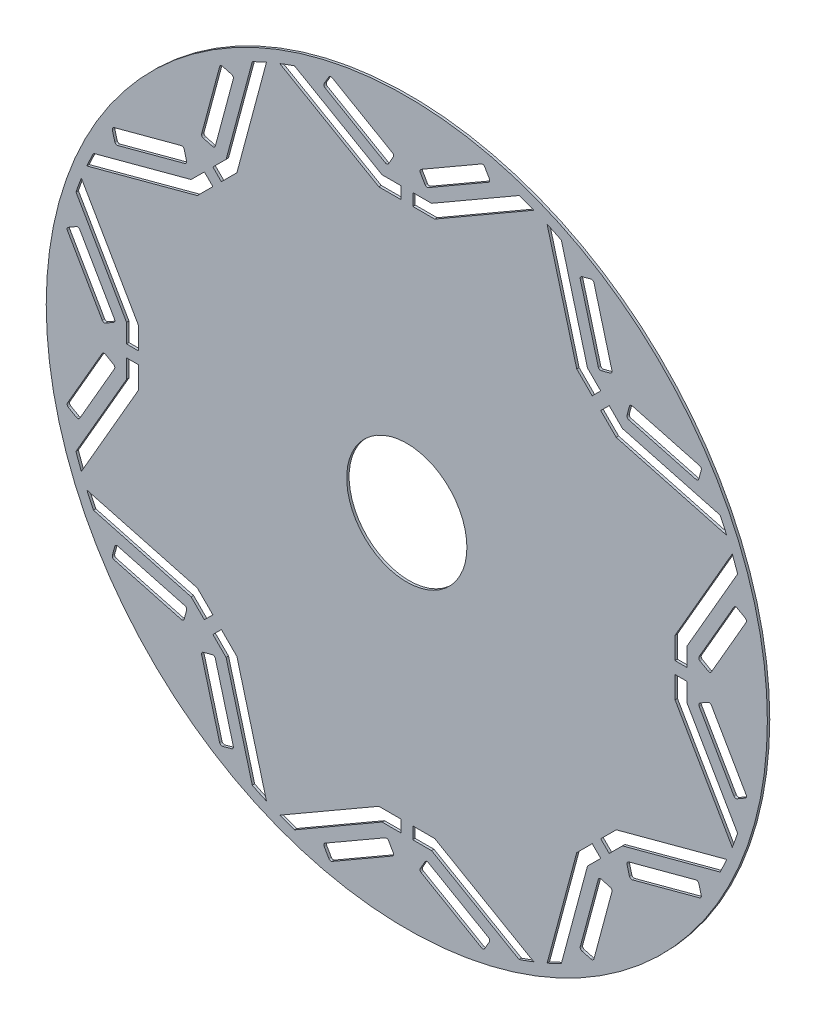
SolidWorks part; units mm, degrees
ref_plane "Front Plane" through (0, 0, 0) normal (0, 0, 1) x (1, 0, 0)
ref_plane "Top Plane" through (0, 0, 0) normal (0, 1, 0) x (1, 0, 0)
ref_plane "Right Plane" through (0, 0, 0) normal (1, 0, 0) x (0, 0, -1)
sketch "Rotor sketch" plane through (0, 0, 0) normal (0, 0, 1) x (1, 0, 0)
  line L0 (0, 0) -> (0, 45) construction
  line L1 (2.6839, 36.4771) -> (10.2011, 40.8171)
  line L2 (2.2741, 36.5869) -> (1.6891, 37.6002)
  line L3 (10.3109, 41.2269) -> (9.7259, 42.2402)
  line L4 (1.7989, 38.01) -> (9.3161, 42.35)
  line L5 (2.4241, 36.3271) -> (9.5759, 42.5) construction
  line L6 (10.4609, 40.9671) -> (1.5391, 37.86) construction
  line L7 (-10.4609, 40.9671) -> (-1.5391, 37.86) construction
  line L8 (-2.4241, 36.3271) -> (-9.5759, 42.5) construction
  line L9 (-1.7989, 38.01) -> (-9.3161, 42.35)
  line L10 (-10.3109, 41.2269) -> (-9.7259, 42.2402)
  line L11 (-2.2741, 36.5869) -> (-1.6891, 37.6002)
  line L12 (-2.6839, 36.4771) -> (-10.2011, 40.8171)
  line L13 (25.6051, 28.1492) -> (23.3585, 36.5334)
  line L14 (24.2628, 27.4789) -> (25.3929, 27.7818)
  line L15 (23.8954, 27.6911) -> (21.6488, 36.0753)
  line L16 (21.861, 36.4427) -> (22.9911, 36.7455)
  line L17 (27.4789, 24.2628) -> (27.7818, 25.3929)
  line L18 (28.1492, 25.6051) -> (36.5334, 23.3585)
  line L19 (36.4427, 21.861) -> (36.7455, 22.9911)
  line L20 (27.6911, 23.8954) -> (36.0753, 21.6488)
  line L21 (38.01, 1.7989) -> (42.35, 9.3161)
  line L22 (36.5869, 2.2741) -> (37.6002, 1.6891)
  line L23 (36.4771, 2.6839) -> (40.8171, 10.2011)
  line L24 (41.2269, 10.3109) -> (42.2402, 9.7259)
  line L25 (36.5869, -2.2741) -> (37.6002, -1.6891)
  line L26 (38.01, -1.7989) -> (42.35, -9.3161)
  line L27 (41.2269, -10.3109) -> (42.2402, -9.7259)
  line L28 (36.4771, -2.6839) -> (40.8171, -10.2011)
  line L29 (28.1492, -25.6051) -> (36.5334, -23.3585)
  line L30 (27.4789, -24.2628) -> (27.7818, -25.3929)
  line L31 (27.6911, -23.8954) -> (36.0753, -21.6488)
  line L32 (36.4427, -21.861) -> (36.7455, -22.9911)
  line L33 (24.2628, -27.4789) -> (25.3929, -27.7818)
  line L34 (25.6051, -28.1492) -> (23.3585, -36.5334)
  line L35 (21.861, -36.4427) -> (22.9911, -36.7455)
  line L36 (23.8954, -27.6911) -> (21.6488, -36.0753)
  line L37 (1.7989, -38.01) -> (9.3161, -42.35)
  line L38 (2.2741, -36.5869) -> (1.6891, -37.6002)
  line L39 (2.6839, -36.4771) -> (10.2011, -40.8171)
  line L40 (10.3109, -41.2269) -> (9.7259, -42.2402)
  line L41 (-2.2741, -36.5869) -> (-1.6891, -37.6002)
  line L42 (-1.7989, -38.01) -> (-9.3161, -42.35)
  line L43 (-10.3109, -41.2269) -> (-9.7259, -42.2402)
  line L44 (-2.6839, -36.4771) -> (-10.2011, -40.8171)
  line L45 (-25.6051, -28.1492) -> (-23.3585, -36.5334)
  line L46 (-24.2628, -27.4789) -> (-25.3929, -27.7818)
  line L47 (-23.8954, -27.6911) -> (-21.6488, -36.0753)
  line L48 (-21.861, -36.4427) -> (-22.9911, -36.7455)
  line L49 (-27.4789, -24.2628) -> (-27.7818, -25.3929)
  line L50 (-28.1492, -25.6051) -> (-36.5334, -23.3585)
  line L51 (-36.4427, -21.861) -> (-36.7455, -22.9911)
  line L52 (-27.6911, -23.8954) -> (-36.0753, -21.6488)
  line L53 (-38.01, -1.7989) -> (-42.35, -9.3161)
  line L54 (-36.5869, -2.2741) -> (-37.6002, -1.6891)
  line L55 (-36.4771, -2.6839) -> (-40.8171, -10.2011)
  line L56 (-41.2269, -10.3109) -> (-42.2402, -9.7259)
  line L57 (-36.5869, 2.2741) -> (-37.6002, 1.6891)
  line L58 (-38.01, 1.7989) -> (-42.35, 9.3161)
  line L59 (-41.2269, 10.3109) -> (-42.2402, 9.7259)
  line L60 (-36.4771, 2.6839) -> (-40.8171, 10.2011)
  line L61 (-28.1492, 25.6051) -> (-36.5334, 23.3585)
  line L62 (-27.4789, 24.2628) -> (-27.7818, 25.3929)
  line L63 (-27.6911, 23.8954) -> (-36.0753, 21.6488)
  line L64 (-36.4427, 21.861) -> (-36.7455, 22.9911)
  line L65 (-24.2628, 27.4789) -> (-25.3929, 27.7818)
  line L66 (-25.6051, 28.1492) -> (-23.3585, 36.5334)
  line L67 (-21.861, 36.4427) -> (-22.9911, 36.7455)
  line L68 (-23.8954, 27.6911) -> (-21.6488, 36.0753)
  line L69 (0, 0) -> (-9.8912, 43.8995) construction
  circle A0 centre (0, 0) radius 45
  circle A1 centre (0, 0) radius 7.5
  arc A2 (-21.861, 36.4427) -> (-21.6488, 36.0753) centre (-21.9386, 36.153) cw
  arc A3 (-23.3585, 36.5334) -> (-22.9911, 36.7455) centre (-23.0688, 36.4558) cw
  arc A4 (-24.2628, 27.4789) -> (-23.8954, 27.6911) centre (-24.1852, 27.7687) ccw
  arc A5 (-25.3929, 27.7818) -> (-25.6051, 28.1492) centre (-25.3153, 28.0715) cw
  arc A6 (-27.4789, 24.2628) -> (-27.6911, 23.8954) centre (-27.7687, 24.1852) cw
  arc A7 (-28.1492, 25.6051) -> (-27.7818, 25.3929) centre (-28.0715, 25.3153) cw
  arc A8 (-36.5334, 23.3585) -> (-36.7455, 22.9911) centre (-36.4558, 23.0688) ccw
  arc A9 (-36.0753, 21.6488) -> (-36.4427, 21.861) centre (-36.153, 21.9386) cw
  arc A10 (-36.5869, 2.2741) -> (-36.4771, 2.6839) centre (-36.7369, 2.5339) ccw
  arc A11 (-37.6002, 1.6891) -> (-38.01, 1.7989) centre (-37.7502, 1.9489) cw
  arc A12 (-41.2269, 10.3109) -> (-40.8171, 10.2011) centre (-41.0769, 10.0511) cw
  arc A13 (-42.35, 9.3161) -> (-42.2402, 9.7259) centre (-42.0902, 9.4661) cw
  arc A14 (-36.5869, -2.2741) -> (-36.4771, -2.6839) centre (-36.7369, -2.5339) cw
  arc A15 (-38.01, -1.7989) -> (-37.6002, -1.6891) centre (-37.7502, -1.9489) cw
  arc A16 (-42.35, -9.3161) -> (-42.2402, -9.7259) centre (-42.0902, -9.4661) ccw
  arc A17 (-40.8171, -10.2011) -> (-41.2269, -10.3109) centre (-41.0769, -10.0511) cw
  arc A18 (-36.5334, -23.3585) -> (-36.7455, -22.9911) centre (-36.4558, -23.0688) cw
  arc A19 (-36.4427, -21.861) -> (-36.0753, -21.6488) centre (-36.153, -21.9386) cw
  arc A20 (-27.4789, -24.2628) -> (-27.6911, -23.8954) centre (-27.7687, -24.1852) ccw
  arc A21 (-27.7818, -25.3929) -> (-28.1492, -25.6051) centre (-28.0715, -25.3153) cw
  arc A22 (-24.2628, -27.4789) -> (-23.8954, -27.6911) centre (-24.1852, -27.7687) cw
  arc A23 (-25.6051, -28.1492) -> (-25.3929, -27.7818) centre (-25.3153, -28.0715) cw
  arc A24 (-23.3585, -36.5334) -> (-22.9911, -36.7455) centre (-23.0688, -36.4558) ccw
  arc A25 (-21.6488, -36.0753) -> (-21.861, -36.4427) centre (-21.9386, -36.153) cw
  arc A26 (-10.3109, -41.2269) -> (-10.2011, -40.8171) centre (-10.0511, -41.0769) cw
  arc A27 (-9.3161, -42.35) -> (-9.7259, -42.2402) centre (-9.4661, -42.0902) cw
  arc A28 (-1.6891, -37.6002) -> (-1.7989, -38.01) centre (-1.9489, -37.7502) cw
  arc A29 (-2.2741, -36.5869) -> (-2.6839, -36.4771) centre (-2.5339, -36.7369) ccw
  arc A30 (10.2011, -40.8171) -> (10.3109, -41.2269) centre (10.0511, -41.0769) cw
  arc A31 (9.3161, -42.35) -> (9.7259, -42.2402) centre (9.4661, -42.0902) ccw
  arc A32 (1.7989, -38.01) -> (1.6891, -37.6002) centre (1.9489, -37.7502) cw
  arc A33 (2.2741, -36.5869) -> (2.6839, -36.4771) centre (2.5339, -36.7369) cw
  arc A34 (23.3585, -36.5334) -> (22.9911, -36.7455) centre (23.0688, -36.4558) cw
  arc A35 (21.861, -36.4427) -> (21.6488, -36.0753) centre (21.9386, -36.153) cw
  arc A36 (24.2628, -27.4789) -> (23.8954, -27.6911) centre (24.1852, -27.7687) ccw
  arc A37 (25.3929, -27.7818) -> (25.6051, -28.1492) centre (25.3153, -28.0715) cw
  arc A38 (28.1492, -25.6051) -> (27.7818, -25.3929) centre (28.0715, -25.3153) cw
  arc A39 (27.4789, -24.2628) -> (27.6911, -23.8954) centre (27.7687, -24.1852) cw
  arc A40 (36.5334, -23.3585) -> (36.7455, -22.9911) centre (36.4558, -23.0688) ccw
  arc A41 (36.0753, -21.6488) -> (36.4427, -21.861) centre (36.153, -21.9386) cw
  arc A42 (41.2269, -10.3109) -> (40.8171, -10.2011) centre (41.0769, -10.0511) cw
  arc A43 (42.35, -9.3161) -> (42.2402, -9.7259) centre (42.0902, -9.4661) cw
  arc A44 (37.6002, -1.6891) -> (38.01, -1.7989) centre (37.7502, -1.9489) cw
  arc A45 (36.5869, -2.2741) -> (36.4771, -2.6839) centre (36.7369, -2.5339) ccw
  arc A46 (38.01, 1.7989) -> (37.6002, 1.6891) centre (37.7502, 1.9489) cw
  arc A47 (36.5869, 2.2741) -> (36.4771, 2.6839) centre (36.7369, 2.5339) cw
  arc A48 (40.8171, 10.2011) -> (41.2269, 10.3109) centre (41.0769, 10.0511) cw
  arc A49 (42.35, 9.3161) -> (42.2402, 9.7259) centre (42.0902, 9.4661) ccw
  arc A50 (36.4427, 21.861) -> (36.0753, 21.6488) centre (36.153, 21.9386) cw
  arc A51 (36.5334, 23.3585) -> (36.7455, 22.9911) centre (36.4558, 23.0688) cw
  arc A52 (27.4789, 24.2628) -> (27.6911, 23.8954) centre (27.7687, 24.1852) ccw
  arc A53 (27.7818, 25.3929) -> (28.1492, 25.6051) centre (28.0715, 25.3153) cw
  arc A54 (24.2628, 27.4789) -> (23.8954, 27.6911) centre (24.1852, 27.7687) cw
  arc A55 (25.6051, 28.1492) -> (25.3929, 27.7818) centre (25.3153, 28.0715) cw
  arc A56 (23.3585, 36.5334) -> (22.9911, 36.7455) centre (23.0688, 36.4558) ccw
  arc A57 (21.6488, 36.0753) -> (21.861, 36.4427) centre (21.9386, 36.153) cw
  arc A58 (10.2011, 40.8171) -> (10.3109, 41.2269) centre (10.0511, 41.0769) ccw
  arc A59 (9.7259, 42.2402) -> (9.3161, 42.35) centre (9.4661, 42.0902) ccw
  arc A60 (1.6891, 37.6002) -> (1.7989, 38.01) centre (1.9489, 37.7502) cw
  arc A61 (2.2741, 36.5869) -> (2.6839, 36.4771) centre (2.5339, 36.7369) ccw
  arc A62 (-10.2011, 40.8171) -> (-10.3109, 41.2269) centre (-10.0511, 41.0769) cw
  arc A63 (-2.6839, 36.4771) -> (-2.2741, 36.5869) centre (-2.5339, 36.7369) ccw
  arc A64 (-1.6891, 37.6002) -> (-1.7989, 38.01) centre (-1.9489, 37.7502) ccw
  arc A65 (-9.7259, 42.2402) -> (-9.3161, 42.35) centre (-9.4661, 42.0902) cw
  point P6 (6, 39.4136)
  point P16 (-6, 39.4136)
  point P74 (0, 0)
  dimension "D6" = 90
  dimension "D7" = 15
  dimension "D10" = 0.3
  dimension "D1" = 9.28
  dimension "D2" = 1.77
  dimension "D3" = 60
  dimension "D4" = 6
  dimension "D5" = 2.5
  dimension "D9" = 1.4346
  dimension "D8" = 8
extrude "Boss-Extrude1" add sketch "Rotor sketch" along normal mid plane 0.3
sketch "Saliency grooves" plane through (0, 0, 0.15) normal (0, 0, 1) x (1, 0, 0)
  line L0 (-12.8371, 38.875) -> (-3.4878, 33.4771)
  line L3 (-14.0139, 41.2864) -> (-3.0859, 34.9771)
  line L4 (0.75, 34.9771) -> (3.0859, 34.9771)
  line L5 (-3.4878, 33.4771) -> (-14.0139, 41.2864) construction
  line L6 (0, 0) -> (0, 45) construction
  line L7 (3.4878, 33.4771) -> (14.0139, 41.2864) construction
  line L8 (-0.75, 33.4771) -> (-3.4878, 33.4771)
  line L9 (14.0139, 41.2864) -> (3.0859, 34.9771)
  line L12 (12.8371, 38.875) -> (3.4878, 33.4771)
  line L13 (-3.0859, 34.9771) -> (-0.75, 34.9771)
  line L14 (3.4878, 33.4771) -> (0.75, 33.4771)
  line L15 (0, 43.6) -> (0, 45) construction
  line L16 (-10.2011, 40.8171) -> (-2.6839, 36.4771) construction
  line L17 (-10.2011, 40.8171) -> (-2.6839, 36.4771) construction
  line L18 (-0.75, 33.4771) -> (0.75, 34.9771) construction
  line L20 (-0.75, 33.4771) -> (-0.75, 34.9771)
  line L22 (0.75, 33.4771) -> (0.75, 34.9771)
  line L23 (-12.8371, 38.875) -> (-15.8526, 40.616)
  line L24 (12.8371, 38.875) -> (15.8526, 40.616)
  line L25 (19.2846, 39.1033) -> (22.5505, 26.9146)
  line L26 (18.4115, 36.566) -> (21.2057, 26.1382)
  line L27 (18.4115, 36.566) -> (17.5103, 39.9293)
  line L28 (23.1416, 24.2022) -> (21.2057, 26.1382)
  line L29 (22.5505, 26.9146) -> (24.2022, 25.2629)
  line L30 (23.1416, 24.2022) -> (24.2022, 25.2629)
  line L31 (25.2629, 24.2022) -> (26.9146, 22.5505)
  line L32 (24.2022, 23.1416) -> (25.2629, 24.2022)
  line L33 (26.1382, 21.2057) -> (24.2022, 23.1416)
  line L34 (36.566, 18.4115) -> (26.1382, 21.2057)
  line L35 (39.1033, 19.2846) -> (26.9146, 22.5505)
  line L36 (36.566, 18.4115) -> (39.9293, 17.5103)
  line L37 (41.2864, 14.0139) -> (34.9771, 3.0859)
  line L38 (38.875, 12.8371) -> (33.4771, 3.4878)
  line L39 (38.875, 12.8371) -> (40.616, 15.8526)
  line L40 (33.4771, 0.75) -> (33.4771, 3.4878)
  line L41 (34.9771, 3.0859) -> (34.9771, 0.75)
  line L42 (33.4771, 0.75) -> (34.9771, 0.75)
  line L43 (34.9771, -0.75) -> (34.9771, -3.0859)
  line L44 (33.4771, -0.75) -> (34.9771, -0.75)
  line L45 (33.4771, -3.4878) -> (33.4771, -0.75)
  line L46 (38.875, -12.8371) -> (33.4771, -3.4878)
  line L47 (41.2864, -14.0139) -> (34.9771, -3.0859)
  line L48 (38.875, -12.8371) -> (40.616, -15.8526)
  line L49 (39.1033, -19.2846) -> (26.9146, -22.5505)
  line L50 (36.566, -18.4115) -> (26.1382, -21.2057)
  line L51 (36.566, -18.4115) -> (39.9293, -17.5103)
  line L52 (24.2022, -23.1416) -> (26.1382, -21.2057)
  line L53 (26.9146, -22.5505) -> (25.2629, -24.2022)
  line L54 (24.2022, -23.1416) -> (25.2629, -24.2022)
  line L55 (24.2022, -25.2629) -> (22.5505, -26.9146)
  line L56 (23.1416, -24.2022) -> (24.2022, -25.2629)
  line L57 (21.2057, -26.1382) -> (23.1416, -24.2022)
  line L58 (18.4115, -36.566) -> (21.2057, -26.1382)
  line L59 (19.2846, -39.1033) -> (22.5505, -26.9146)
  line L60 (18.4115, -36.566) -> (17.5103, -39.9293)
  line L61 (14.0139, -41.2864) -> (3.0859, -34.9771)
  line L62 (12.8371, -38.875) -> (3.4878, -33.4771)
  line L63 (12.8371, -38.875) -> (15.8526, -40.616)
  line L64 (0.75, -33.4771) -> (3.4878, -33.4771)
  line L65 (3.0859, -34.9771) -> (0.75, -34.9771)
  line L66 (0.75, -33.4771) -> (0.75, -34.9771)
  line L67 (-0.75, -34.9771) -> (-3.0859, -34.9771)
  line L68 (-0.75, -33.4771) -> (-0.75, -34.9771)
  line L69 (-3.4878, -33.4771) -> (-0.75, -33.4771)
  line L70 (-12.8371, -38.875) -> (-3.4878, -33.4771)
  line L71 (-14.0139, -41.2864) -> (-3.0859, -34.9771)
  line L72 (-12.8371, -38.875) -> (-15.8526, -40.616)
  line L73 (-19.2846, -39.1033) -> (-22.5505, -26.9146)
  line L74 (-18.4115, -36.566) -> (-21.2057, -26.1382)
  line L75 (-18.4115, -36.566) -> (-17.5103, -39.9293)
  line L76 (-23.1416, -24.2022) -> (-21.2057, -26.1382)
  line L77 (-22.5505, -26.9146) -> (-24.2022, -25.2629)
  line L78 (-23.1416, -24.2022) -> (-24.2022, -25.2629)
  line L79 (-25.2629, -24.2022) -> (-26.9146, -22.5505)
  line L80 (-24.2022, -23.1416) -> (-25.2629, -24.2022)
  line L81 (-26.1382, -21.2057) -> (-24.2022, -23.1416)
  line L82 (-36.566, -18.4115) -> (-26.1382, -21.2057)
  line L83 (-39.1033, -19.2846) -> (-26.9146, -22.5505)
  line L84 (-36.566, -18.4115) -> (-39.9293, -17.5103)
  line L85 (-41.2864, -14.0139) -> (-34.9771, -3.0859)
  line L86 (-38.875, -12.8371) -> (-33.4771, -3.4878)
  line L87 (-38.875, -12.8371) -> (-40.616, -15.8526)
  line L88 (-33.4771, -0.75) -> (-33.4771, -3.4878)
  line L89 (-34.9771, -3.0859) -> (-34.9771, -0.75)
  line L90 (-33.4771, -0.75) -> (-34.9771, -0.75)
  line L91 (-34.9771, 0.75) -> (-34.9771, 3.0859)
  line L92 (-33.4771, 0.75) -> (-34.9771, 0.75)
  line L93 (-33.4771, 3.4878) -> (-33.4771, 0.75)
  line L94 (-38.875, 12.8371) -> (-33.4771, 3.4878)
  line L95 (-41.2864, 14.0139) -> (-34.9771, 3.0859)
  line L96 (-38.875, 12.8371) -> (-40.616, 15.8526)
  line L97 (-39.1033, 19.2846) -> (-26.9146, 22.5505)
  line L98 (-36.566, 18.4115) -> (-26.1382, 21.2057)
  line L99 (-36.566, 18.4115) -> (-39.9293, 17.5103)
  line L100 (-24.2022, 23.1416) -> (-26.1382, 21.2057)
  line L101 (-26.9146, 22.5505) -> (-25.2629, 24.2022)
  line L102 (-24.2022, 23.1416) -> (-25.2629, 24.2022)
  line L103 (-24.2022, 25.2629) -> (-22.5505, 26.9146)
  line L104 (-23.1416, 24.2022) -> (-24.2022, 25.2629)
  line L105 (-21.2057, 26.1382) -> (-23.1416, 24.2022)
  line L106 (-18.4115, 36.566) -> (-21.2057, 26.1382)
  line L107 (-19.2846, 39.1033) -> (-22.5505, 26.9146)
  line L108 (-18.4115, 36.566) -> (-17.5103, 39.9293)
  circle A0 centre (0, 0) radius 45 construction
  circle A1 centre (0, 0) radius 43.6
  point P1 (-9.1257, 37.6599)
  point P15 (9.1257, 37.6599)
  point P24 (0, 34.2271)
  point P27 (-18.9061, 24.2013)
  point P28 (0, 0)
  point P128 (0, 0)
  dimension "D1" = 1.4
  dimension "D2" = 1.5
  dimension "D3" = 1.5
  dimension "D4" = 1.5
  dimension "D5" = 1.5
  dimension "D6" = 1.5
  dimension "D7" = 8
extrude "Cut-Extrude1" cut sketch "Saliency grooves" against normal through all contours L97 A1 L99 L98 L100 L102 L101 | L108 A1 L107 L103 L104 L105 L106 | L24 A1 L9 L4 L22 L14 L12 | L3 A1 L23 L0 L8 L20 L13 | L25 A1 L27 L26 L28 L30 L29 | L36 A1 L35 L31 L32 L33 L34 | L37 A1 L39 L38 L40 L42 L41 | L48 A1 L47 L43 L44 L45 L46 | L96 A1 L95 L91 L92 L93 L94 | L85 A1 L87 L86 L88 L90 L89 | L84 A1 L83 L79 L80 L81 L82 | L73 A1 L75 L74 L76 L78 L77 | L72 A1 L71 L67 L68 L69 L70 | L61 A1 L63 L62 L64 L66 L65 | L60 A1 L59 L55 L56 L57 L58 | L49 A1 L51 L50 L52 L54 L53 region at (-7.9988, 37.0454, 0.15) region at (-20.539, 31.8511, 0.15) region at (7.9988, 37.0454, 0.15) region at (-31.8511, 20.539, 0.15) region at (20.539, 31.8511, 0.15) region at (-37.0454, 7.9988, 0.15) region at (31.8511, 20.539, 0.15) region at (-37.0454, -7.9988, 0.15) region at (37.0454, 7.9988, 0.15) region at (-31.8511, -20.539, 0.15) region at (37.0454, -7.9988, 0.15) region at (-20.539, -31.8511, 0.15) region at (31.8511, -20.539, 0.15) region at (-7.9988, -37.0454, 0.15) region at (20.539, -31.8511, 0.15) region at (7.9988, -37.0454, 0.15)
equation "\"Magnet thickness\"= 1.57mm"
equation "\"Magnet short side\"= 9.08mm"
equation "\"Magnet long side\"= 19.14mm"
equation "\"D2@Rotor sketch\"=\"Magnet thickness\" + 0.2"
equation "\"Magnet angle\" = 60deg"
equation "\"Magnet distance from center\"= 6mm"
equation "\"Magnet distance from top\"= 2.5mm"
equation "\"D1@Rotor sketch\"=\"Magnet short side\" +0.2"
equation "\"D4@Rotor sketch\"=\"Magnet distance from center\""
equation "\"D3@Rotor sketch\"=\"Magnet angle\""
equation "\"Rotor outer Φ\"= 90mm"
equation "\"Rotor inner Φ\"= 15mm"
equation "\"D7@Rotor sketch\"=\"Rotor inner Φ\""
equation "\"D6@Rotor sketch\"=\"Rotor outer Φ\""
equation "\"Lamination thickness\"= 0.3mm"
equation "\"D1@Boss-Extrude1\"=\"Lamination thickness\""
equation "\"D5@Rotor sketch\"=\"Magnet distance from top\""
equation "\"Magnet hole fillet\"= 0.3mm"
equation "\"D10@Rotor sketch\"=\"Magnet hole fillet\""
equation "\"V pair count\"= 8"
equation "\"D8@Rotor sketch\"=\"V pair count\""
equation "\"Bridge thickness\"= 1.4mm"
equation "\"Groove thickness\" = 1.5mm"
equation "\"Center bridge width\"= 1.5mm"
equation "\"Groove-magnet clearance\"= 1.5mm"
equation "\"D1@Saliency grooves\"=\"Bridge thickness\""
equation "\"D2@Saliency grooves\"=\"Groove thickness\""
equation "\"D3@Saliency grooves\"=\"Center bridge width\""
equation "\"D4@Saliency grooves\"=\"Groove-magnet clearance\""
equation "\"D5@Saliency grooves\"=\"Groove-magnet clearance\""
equation "\"D6@Saliency grooves\"=\"Groove thickness\""
